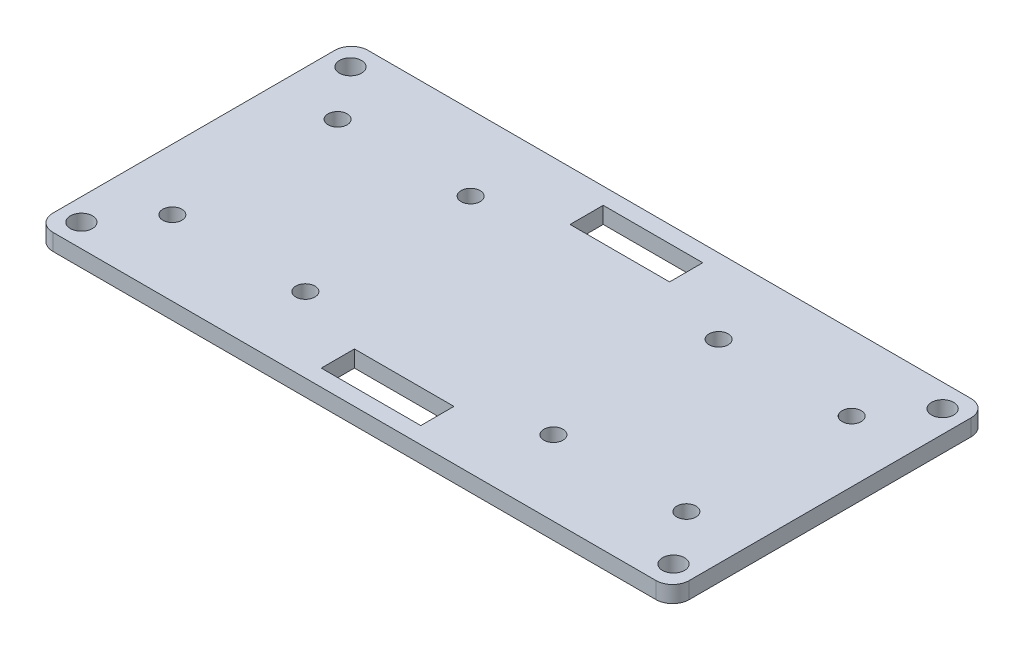
SolidWorks part; units mm, degrees
ref_plane "Plano frontal" through (0, 0, 0) normal (0, 0, 1) x (1, 0, 0)
ref_plane "Plano superior" through (0, 0, 0) normal (0, 1, 0) x (1, 0, 0)
ref_plane "Plano direito" through (0, 0, 0) normal (1, 0, 0) x (0, 0, -1)
sketch "Esboço1" plane through (0, 0, 0) normal (0, 1, 0) x (1, 0, 0)
  line L7 (-57.5484, 29.5) -> (57.5484, 29.5)
  line L8 (57.5484, 29.5) -> (57.5484, -27.5)
  line L9 (57.5484, -27.5) -> (-57.5484, -27.5)
  line L10 (-57.5484, -27.5) -> (-57.5484, 29.5)
  line L11 (0, 29.5) -> (0, -27.5) construction
  line L12 (-57.5484, 1) -> (57.5484, 1) construction
  dimension "D1" = 57
  dimension "D2" = 115.0968
extrude "Ressalto-extrusão1" add sketch "Esboço1" along normal blind 3
sketch "Esboço2" plane through (0, 3, 0) normal (0, 1, 0) x (1, 0, 0)
  line L0 (0, 29.5) -> (0, -27.5) construction
  line L1 (57.5484, 29.5) -> (-57.5484, 29.5) construction
  line L2 (-57.5484, -27.5) -> (57.5484, -27.5) construction
  circle A0 centre (-46.4884, 15.945) radius 1.73
  circle A1 centre (-22.4284, 15.945) radius 1.73
  circle A2 centre (-22.4284, -13.945) radius 1.73
  circle A5 centre (22.4284, -13.945) radius 1.73
  circle A6 centre (22.4284, 15.945) radius 1.73
  circle A7 centre (46.4884, 15.945) radius 1.73
  circle A8 centre (-46.4884, -13.945) radius 1.73
  circle A9 centre (46.4884, -13.945) radius 1.73
extrude "Corte-extrusão1" cut sketch "Esboço2" against normal through all
sketch "Esboço3" plane through (0, 0, 0) normal (0, -1, 0) x (1, 0, 0)
  line L0 (0, 27.5) -> (0, 24.5) construction
  line L1 (-57.5484, 27.5) -> (57.5484, 27.5) construction
  line L2 (-9, 24.5) -> (9, 24.5)
  line L3 (9, 24.5) -> (9, 18.5)
  line L4 (-9, 24.5) -> (-9, 18.5)
  line L5 (-9, 18.5) -> (9, 18.5)
  line L6 (-57.5484, -1) -> (57.5484, -1) construction
  line L7 (-57.5484, -29.5) -> (-57.5484, 27.5) construction
  line L8 (57.5484, 27.5) -> (57.5484, -29.5) construction
  line L9 (9, 24.5) -> (9, 18.5)
  line L10 (-9, 24.5) -> (-9, 18.5)
  line L11 (9, 24.5) -> (9, 18.5)
  line L12 (-9, 24.5) -> (-9, 18.5)
  line L13 (9, 24.5) -> (9, 18.5)
  line L14 (-9, 24.5) -> (-9, 18.5)
  line L15 (0, -29.5) -> (0, -26.5) construction
  line L16 (-9, -26.5) -> (-9, -20.5)
  line L17 (9, -26.5) -> (9, -20.5)
  line L18 (-9, -26.5) -> (-9, -20.5)
  line L19 (9, -26.5) -> (9, -20.5)
  line L20 (-9, -26.5) -> (-9, -20.5)
  line L21 (9, -26.5) -> (9, -20.5)
  line L22 (-9, -20.5) -> (9, -20.5)
  line L23 (-9, -26.5) -> (-9, -20.5)
  line L24 (9, -26.5) -> (9, -20.5)
  line L25 (-9, -26.5) -> (9, -26.5)
  point P8 (0, 24.5)
  point P22 (0, -26.5)
  dimension "D1" = 3
  dimension "D2" = 18
  dimension "D3" = 6
extrude "Corte-extrusão2" cut sketch "Esboço3" against normal through all contours L4 L5 L3 L2 | L16 L25 L17 L22 region at (0, 0, 21.5) region at (0, 0, -23.5)
sketch "Esboço5" plane through (0, 3, 0) normal (0, 1, 0) x (1, 0, 0)
  line L0 (53.5484, 21.175) -> (53.5484, 29.5) construction
  line L1 (19.1984, 21.175) -> (47.5484, 21.175) construction
  line L2 (57.5484, 29.5) -> (-57.5484, 29.5) construction
  line L3 (57.5484, -27.5) -> (57.5484, 29.5) construction
  line L4 (57.5484, 1) -> (-57.5484, 1) construction
  line L5 (-57.5484, 29.5) -> (-57.5484, -27.5) construction
  line L6 (0, 29.5) -> (0, -27.5) construction
  line L7 (-57.5484, -27.5) -> (57.5484, -27.5) construction
  line L8 (53.5484, -19.175) -> (53.5484, -27.5) construction
  line L9 (-53.5484, -19.175) -> (-53.5484, -27.5) construction
  line L10 (-53.5484, 21.175) -> (-53.5484, 29.5) construction
  circle A0 centre (53.5484, 25.3375) radius 2
  circle A1 centre (53.5484, -23.3375) radius 2
  circle A2 centre (-53.5484, -23.3375) radius 2
  circle A3 centre (-53.5484, 25.3375) radius 2
  dimension "D2" = 4
  dimension "D1" = 4
extrude "Corte-extrusão3" cut sketch "Esboço5" against normal through all
fillet "Filete1" radius 3 4 edges at (57.5484, 1.5, -29.5) (57.5484, 1.5, 27.5) (-57.5484, 1.5, 27.5) (-57.5484, 1.5, -29.5)
